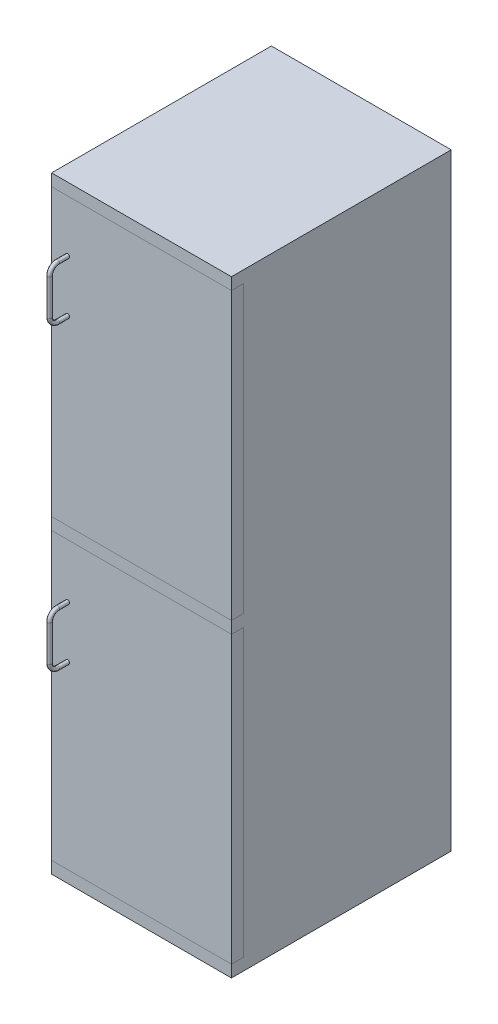
SolidWorks part; units mm, degrees
ref_plane "Front Plane" through (0, 0, 0) normal (0, 0, 1) x (1, 0, 0)
ref_plane "Top Plane" through (0, 0, 0) normal (0, 1, 0) x (1, 0, 0)
ref_plane "Right Plane" through (0, 0, 0) normal (1, 0, 0) x (0, 0, -1)
sketch "Sketch1" plane through (0, 0, 0) normal (0, 0, 1) x (1, 0, 0)
  line L1 (0, 0) -> (450, 0)
  line L2 (0, 0) -> (0, 1520)
  line L3 (0, 1520) -> (450, 1520)
  line L4 (450, 0) -> (450, 1520)
  dimension "D1" = 450
  dimension "D2" = 1520
extrude "Boss-Extrude1" add sketch "Sketch1" against normal blind 550 contours L2 L1 L4 L3
sketch "Sketch2" plane through (0, 0, 0) normal (0, 0, 1) x (1, 0, 0)
  line L0 (450, 0) -> (450, 1520) construction
  line L1 (0, 1490) -> (450, 1490)
  line L2 (0, 1490) -> (0, 775)
  line L3 (0, 775) -> (450, 775)
  line L4 (450, 1490) -> (450, 775)
  line L5 (0, 0) -> (0, 1520) construction
  line L10 (0, 0) -> (450, 0) construction
  line L11 (0, 1520) -> (450, 1520) construction
  line L13 (0, 745) -> (0, 30)
  line L14 (0, 745) -> (450, 745)
  line L15 (450, 745) -> (450, 30)
  line L16 (0, 30) -> (450, 30)
  point P6 (40, 1230)
  point P7 (0, 0)
  point P8 (0, 0)
  point P16 (40, 1360)
  point P19 (40, 485)
  point P20 (40, 615)
  point P22 (0, 0)
  dimension "D1" = 130
  dimension "D2" = 40
  dimension "D3" = 30
  dimension "D4" = 130
  dimension "D6" = 30
  dimension "D7" = 30
  dimension "D5" = 2
extrude "Cut-Extrude1" cut sketch "Sketch2" against normal blind 30
extrude "Boss-Extrude2" add sketch "Sketch2<2>" against normal up to surface (30 mm away) separate body up to face at (225, 1132.5, -30)
sketch "Sketch2<2>" plane through (0, 0, 0) normal (0, 0, 1) x (1, 0, 0) same geometry as "Sketch2"
ref_plane "Plane1" through (40, 0, 0) normal (-1, 0, 0) x (0, 0, 1)
sketch "Sketch3" plane through (40, 0, 0) normal (-1, 0, 0) x (0, 0, 1)
  line L0 (0, 1360) -> (25, 1360)
  line L1 (45, 1340) -> (45, 1250)
  line L2 (25, 1230) -> (0, 1230)
  line L3 (0, 1490) -> (0, 775) construction
  arc A0 (25, 1360) -> (45, 1340) centre (25, 1340) cw
  arc A1 (45, 1250) -> (25, 1230) centre (25, 1250) cw
  point P11 (45, 1230)
  dimension "D1" = 20
  dimension "D2" = 45
sketch "Sketch4" plane through (0, 0, 0) normal (0, 0, 1) x (1, 0, 0)
  circle A0 centre (40, 1360) radius 5
  dimension "D1" = 10
sweep "Sweep5" add profiles "Sketch4" path "Sketch3"
pattern_linear "LPattern1" count 2 spacing 750 along (0, -1, 0) of "Sweep5"
